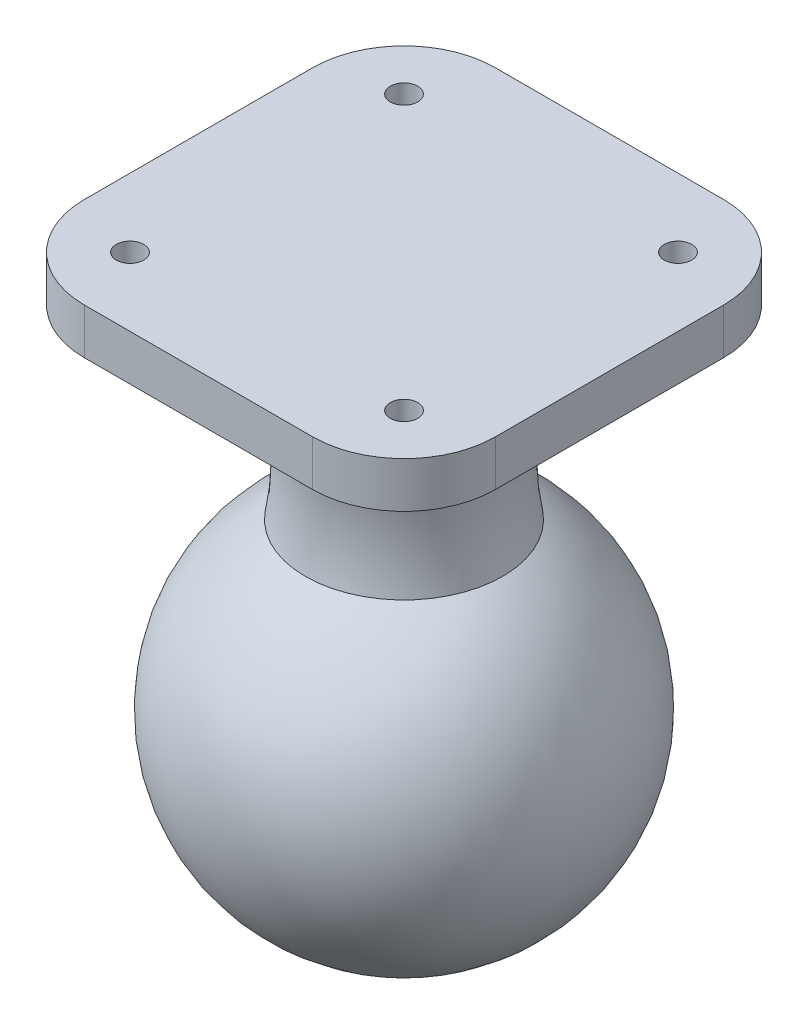
SolidWorks part; units mm, degrees
ref_plane "Front Plane" through (0, 0, 0) normal (0, 0, 1) x (1, 0, 0)
ref_plane "Top Plane" through (0, 0, 0) normal (0, 1, 0) x (1, 0, 0)
ref_plane "Right Plane" through (0, 0, 0) normal (1, 0, 0) x (0, 0, -1)
sketch "Sketch1" plane through (0, 0, 0) normal (0, 1, 0) x (1, 0, 0)
  line L0 (0, 21.0626) -> (0, -19.8901) construction
  line L1 (-21.7744, 0) -> (20.5182, 0) construction
  line L3 (12.5, -22.5) -> (-12.5, -22.5)
  line L4 (22.5, -12.5) -> (22.5, 12.5)
  line L5 (12.5, 22.5) -> (-12.5, 22.5)
  line L6 (-22.5, -12.5) -> (-22.5, 12.5)
  line L7 (22.5, -22.5) -> (-22.5, 22.5) construction
  line L8 (22.5, 22.5) -> (-22.5, -22.5) construction
  circle A1 centre (-15, 15) radius 1.5
  circle A2 centre (15, 15) radius 1.5
  circle A3 centre (15, -15) radius 1.5
  circle A4 centre (-15, -15) radius 1.5
  arc A5 (22.5, 12.5) -> (12.5, 22.5) centre (12.5, 12.5) ccw
  arc A6 (12.5, -22.5) -> (22.5, -12.5) centre (12.5, -12.5) ccw
  arc A7 (-12.5, -22.5) -> (-22.5, -12.5) centre (-12.5, -12.5) cw
  arc A8 (-12.5, 22.5) -> (-22.5, 12.5) centre (-12.5, 12.5) ccw
  point P0 (0, 0)
  dimension "D1" = 3
  dimension "D2" = 45
  dimension "D3" = 45
  dimension "D4" = 10
extrude "Boss-Extrude1" add sketch "Sketch1" along normal blind 5
sketch "Sketch5" plane through (0, 0, 0) normal (0, 0, 1) x (1, 0, 0)
  line L0 (-12.5, 0) -> (12.5, 0) construction
  line L3 (0, 0) -> (0, -30)
  line L4 (0, -30) -> (-14.4909, -30)
  line L5 (0, 0) -> (-14.4909, 0)
  line L6 (0, 6.6232) -> (0, -25.0787) construction
  line L7 (-22.5, 0) -> (-12.5, 0) construction
  arc A0 (-14.4909, 0) -> (-14.4909, -30) centre (-39.3102, -15) cw
  dimension "D3" = 29
  dimension "D1" = 30
  dimension "D5" = 0
revolve "Revolve5" add sketch "Sketch5" angle 360 about L6
sketch "Sketch6" plane through (0, 0, 0) normal (1, 0, 0) x (0, 0, -1)
  line L1 (0, -17.3238) -> (0, -59.1192)
  line L2 (0, -62.9626) -> (0, -9.2015) construction
  arc A3 (0, -17.3238) -> (0, -59.1192) centre (0, -38.2215) ccw
revolve "Revolve6" add sketch "Sketch6" angle 360 about L2
